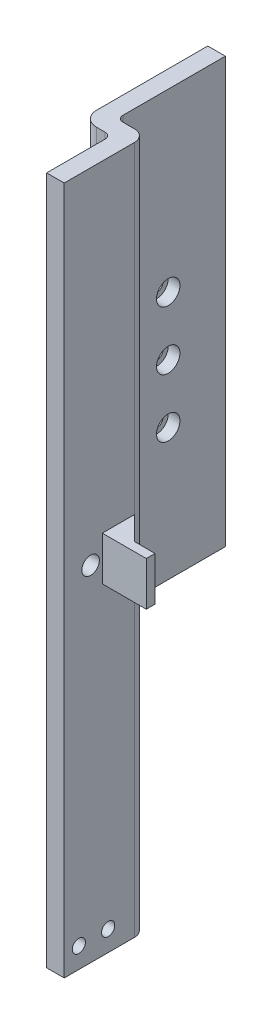
SolidWorks part; units mm, degrees
ref_plane "Piano frontale" through (0, 0, 0) normal (0, 0, 1) x (1, 0, 0)
ref_plane "Piano superiore" through (0, 0, 0) normal (0, 1, 0) x (1, 0, 0)
ref_plane "Piano destro" through (0, 0, 0) normal (1, 0, 0) x (0, 0, -1)
ref_plane "Piano1" through (0, 0, 0) normal (-1, 0, 0) x (0, -1, 0)
sketch "Schizzo1" plane through (0, 0, 0) normal (-1, 0, 0) x (0, -1, 0)
  line L0 (0, -43) -> (0, 22)
  line L1 (0, 22) -> (-235, 22)
  line L2 (-235, 22) -> (-235, -43)
  line L3 (-235, -43) -> (0, -43)
  dimension "D1" = 235
  dimension "D2" = 65
extrude "Estrusione-Estrusione1" add sketch "Schizzo1" against normal blind 16
sketch "Schizzo2" plane through (0, 0, 0) normal (0, -1, 0) x (1, 0, 0)
  line L0 (16, -43) -> (16, -6)
  line L1 (16, -6) -> (6, -6)
  line L2 (6, -6) -> (6, -43)
  line L3 (6, -43) -> (16, -43)
  line L4 (0, -43) -> (0, 22) construction
  dimension "D1" = 6
  dimension "D2" = 16
  dimension "D3" = 37
extrude "Taglio-Estrusione1" cut sketch "Schizzo2" against normal through all
sketch "Schizzo3" plane through (0, 0, 0) normal (-1, 0, 0) x (0, 0, 1)
  line L0 (-8, 0) -> (-8, 90)
  line L1 (-8, 90) -> (-43, 90)
  line L2 (-43, 90) -> (-43, 0)
  line L3 (-43, 0) -> (-8, 0)
  line L4 (-43, 0) -> (22, 0) construction
  line L5 (-43, 235) -> (-43, 0) construction
  dimension "D1" = 35
  dimension "D2" = 90
extrude "Taglio-Estrusione2" cut sketch "Schizzo3" against normal through all
sketch "Schizzo4" plane through (0, 0, 0) normal (0, -1, 0) x (1, 0, 0)
  line L0 (0, 0) -> (10, 0)
  line L1 (10, 0) -> (10, 22)
  line L2 (10, 22) -> (0, 22)
  line L3 (0, 22) -> (0, 0)
  line L4 (6, -6) -> (6, -8) construction
  line L5 (16, -6) -> (6, -6) construction
  dimension "D1" = 4
  dimension "D2" = 6
  dimension "D3" = 6
  dimension "D4" = 28
extrude "Taglio-Estrusione3" cut sketch "Schizzo4" against normal through all
hole_wizard "Foro lamato per Vite M4 a testa esagonale-1" positions "Schizzo6" profile "Schizzo5" counterbore size "M4" standard "Ansi Metric"
sketch "Schizzo6" plane through (6, 0, 0) normal (1, 0, 0) x (0, 0, -1)
  point P0 (23.5, 175)
  point P1 (23.5, 155)
  point P2 (23.5, 135)
sketch "Schizzo5" plane through (6, 175, -23.5) normal (0, 1, 0) x (0, 0, -1)
  line L0 (0, 0) -> (0, 6)
  line L1 (0, 6) -> (2.25, 6)
  line L3 (2.25, 6) -> (2.25, 4)
  line L4 (2.25, 4) -> (4, 4)
  line L5 (4, 4) -> (4, 0)
  line L7 (4, 0) -> (0, 0)
  line L11 (0, -6.35) -> (0, 107.95) construction
  dimension "Thru Hole Dia." = 4.5
  dimension "Thru Hole Depth" = 6
  dimension "C'Bore Dia." = 8
  dimension "C'Bore Depth" = 4
fillet "Raccordo1" radius 2 2 edges at (10, 117.5, 0) (6, 117.5, -6) tangent propagation no
fillet "Raccordo2" radius 4 1 edges at (16, 117.5, -6) tangent propagation no
fillet "Raccordo3" radius 5 1 edges at (0, 117.5, 0) tangent propagation no
fillet "Raccordo4" radius 6 1 edges at (3, 90, -8) tangent propagation no
hole_wizard "Foro per Vite M4-1" positions "Schizzo7" profile "Schizzo8" hole size "M4" standard "ISO"
sketch "Schizzo7" plane through (10, 0, 0) normal (-1, 0, 0) x (0, 0, 1)
  line L0 (2, 0) -> (22, 0) construction
  line L1 (22, 235) -> (22, 0) construction
  point P0 (17, 7)
  point P7 (7, 7)
  dimension "D1" = 7
  dimension "D2" = 5
  dimension "D3" = 10
  dimension "D4" = 7
sketch "Schizzo8" plane through (10, 7, 17) normal (0, 1, 0) x (0, 0, 1)
  line L0 (0, 0) -> (0, 189.3519)
  line L1 (0, 189.3519) -> (2.25, 188)
  line L2 (2.25, 188) -> (2.25, 0)
  line L5 (2.25, 0) -> (0, 0)
  line L10 (0, 189.3519) -> (-2.25, 188) construction
  line L11 (0, -6.35) -> (0, 107.95) construction
  dimension "Hole Dia." = 4.5
  dimension "Hole Depth" = 188
  dimension "Drill Angle" = 118
sketch "Schizzo9" plane through (16, 0, 0) normal (1, 0, 0) x (0, 0, -1)
  line L0 (2, 0) -> (2, 235) construction
  line L1 (-9, 110) -> (-6, 110)
  line L2 (-9, 110) -> (-9, 125)
  line L3 (-9, 125) -> (-6, 125)
  line L4 (-6, 110) -> (-6, 125)
  line L5 (2, 0) -> (-22, 0) construction
  dimension "D1" = 15
  dimension "D2" = 3
  dimension "D3" = 8
  dimension "D4" = 110
extrude "Estrusione-Estrusione2" add sketch "Schizzo9" along normal blind 15
sketch "Schizzo10" plane through (16, 0, 0) normal (1, 0, 0) x (0, 0, -1)
  line L0 (-9, 125) -> (-9, 110) construction
  line L1 (-13, 117.5) -> (-9, 117.5) construction
  circle A0 centre (-13, 117.5) radius 3
  point P5 (-13.3774, 117.5)
  dimension "D1" = 6
  dimension "D2" = 4
extrude "Taglio-Estrusione4" cut sketch "Schizzo10" against normal blind 15
chamfer "Smusso1" distance 8 angle 45 1 edges at (16, 117.5, 6)
